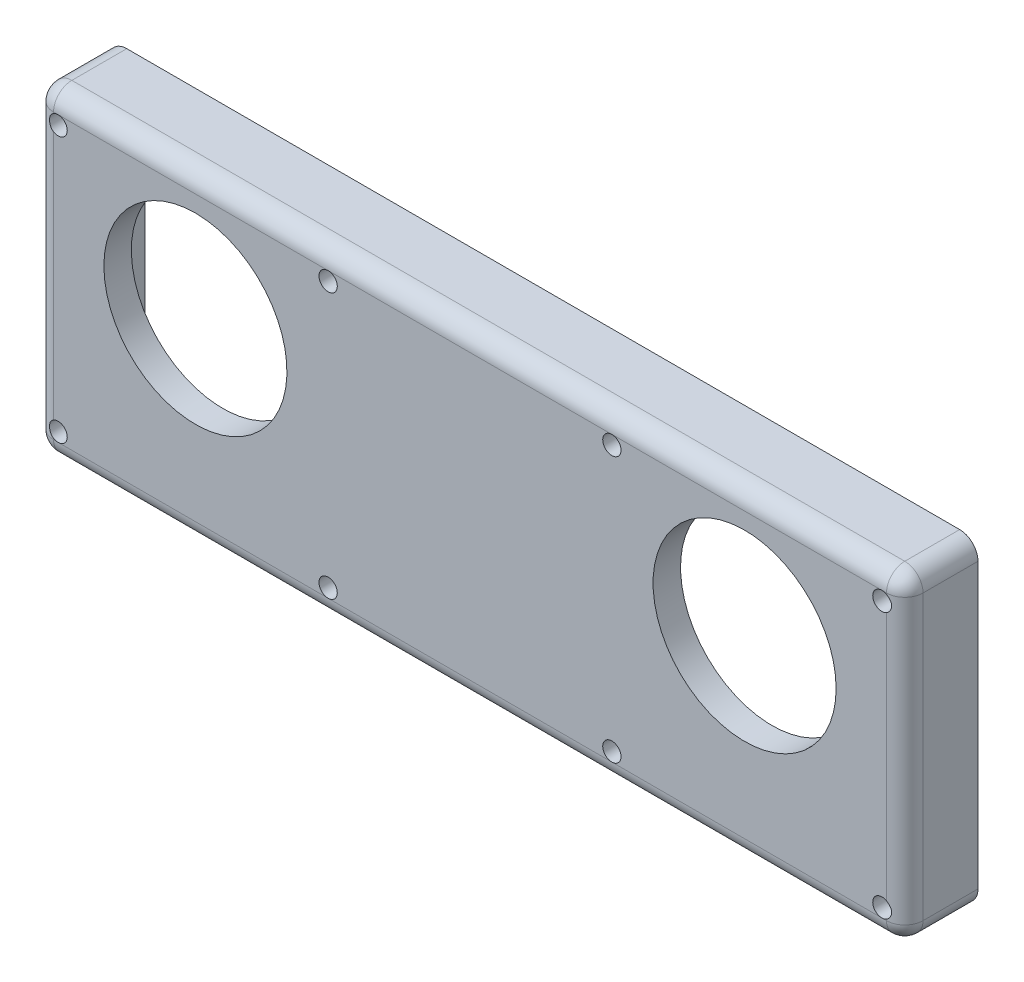
SolidWorks part; units mm, degrees
ref_plane "Front Plane" through (0, 0, 0) normal (0, 0, 1) x (1, 0, 0)
ref_plane "Top Plane" through (0, 0, 0) normal (0, 1, 0) x (1, 0, 0)
ref_plane "Right Plane" through (0, 0, 0) normal (1, 0, 0) x (0, 0, -1)
sketch "Sketch2" plane through (0, 0, 0) normal (0, 0, 1) x (1, 0, 0)
  line L0 (-59.1429, 44.8314) -> (33.8571, 44.8314)
  line L1 (33.8571, 44.8314) -> (33.8571, 12.8314)
  line L2 (33.8571, 12.8314) -> (-59.1429, 12.8314)
  line L3 (-59.1429, 12.8314) -> (-59.1429, 44.8314)
  circle A0 centre (-57.6429, 43.3314) radius 1
  circle A1 centre (-57.6429, 14.3314) radius 1
  circle A2 centre (-28.1429, 43.3314) radius 1
  circle A3 centre (2.8571, 43.3314) radius 1
  circle A4 centre (2.8571, 14.3314) radius 1
  circle A5 centre (-28.1429, 14.3314) radius 1
  circle A6 centre (32.3571, 14.3314) radius 1
  circle A7 centre (32.3571, 43.3314) radius 1
extrude "Boss-Extrude1" add sketch "Sketch2" along normal blind 3
sketch "Sketch6" plane through (0, 0, 3) normal (0, 0, 1) x (1, 0, 0)
  line L0 (-12.6429, 44.8314) -> (33.8571, 28.8314)
  line L1 (33.8571, 44.8314) -> (-59.1429, 44.8314) construction
  line L2 (33.8571, 12.8314) -> (33.8571, 44.8314) construction
  line L3 (33.8571, 28.8314) -> (-12.6429, 29.5401)
  line L5 (-60.1429, 12.0401) -> (34.8571, 12.0401)
  line L6 (-60.1429, 12.0401) -> (-60.1429, 47.0401)
  line L7 (-60.1429, 47.0401) -> (34.8571, 47.0401)
  line L8 (34.8571, 12.0401) -> (34.8571, 47.0401)
  line L9 (-60.1429, 12.0401) -> (34.8571, 47.0401) construction
  line L10 (-60.1429, 47.0401) -> (34.8571, 12.0401) construction
  line M1 (-59.1429, 44.8314) -> (-59.1429, 12.8314)
  line M2 (-59.1429, 12.8314) -> (33.8571, 12.8314)
  line M3 (33.8571, 12.8314) -> (33.8571, 44.8314)
  line M4 (33.8571, 44.8314) -> (-59.1429, 44.8314)
extrude "Boss-Extrude2" add sketch "Sketch6" against normal up to surface (3 mm away) contours L5 L8 L7 L6 M1 M4 M3 M2 region at (-60.0417, 29.5401, 3) up to face at (33.3571, 14.3314, 0)
sketch "Sketch8" plane through (0, 0, 0) normal (0, 0, -1) x (-1, 0, 0)
  line L0 (-34.8571, 47.0401) -> (-34.8571, 46.3314)
  line L1 (-34.8571, 12.0401) -> (-34.8571, 47.0401) construction
  line L2 (-32.8571, 46.3314) -> (58.1429, 46.3314) construction
  line L3 (-34.8571, 46.3314) -> (60.1429, 46.3314)
  line L4 (60.1429, 12.0401) -> (60.1429, 47.0401) construction
  line L5 (60.1429, 46.3314) -> (60.1429, 47.0401)
  line L6 (60.1429, 47.0401) -> (-34.8571, 47.0401)
extrude "Cut-Extrude6" cut sketch "Sketch8" against normal blind 10
sketch "Sketch9" plane through (0, 0, 3) normal (0, 0, 1) x (1, 0, 0)
  line L0 (34.8571, 12.0401) -> (34.8571, 11.3301)
  line L1 (-60.1429, 12.0401) -> (34.8571, 12.0401)
  line L2 (34.8571, 11.3301) -> (-60.1429, 11.3301)
  line L3 (-60.1429, 11.3301) -> (-60.1429, 12.0401)
extrude "Boss-Extrude3" add sketch "Sketch9" against normal up to surface (3 mm away) up to face at (-12.6429, 29.1858, 0)
sketch "Sketch10" plane through (0, 0, 3) normal (0, 0, 1) x (1, 0, 0)
  line L0 (-12.6429, 46.3314) -> (-68.5519, 3.7684)
  line L1 (34.8571, 46.3314) -> (-60.1429, 46.3314) construction
  line L2 (-68.5519, 3.7684) -> (-68.5519, 46.3314)
  line L3 (-68.5519, 46.3314) -> (17.3571, 46.3314)
  line L4 (17.3571, 46.3314) -> (17.3571, 32.5314)
  circle A0 centre (-68.5519, 3.7684) radius 10
  circle A1 centre (17.3571, 32.5314) radius 10
extrude "Cut-Extrude7" cut sketch "Sketch10" against normal blind 10 contours L2 A0 L0 | L0 A0 L2 | A1 region at (24.2282, 39.4025, 3) region at (-69.042, 2.7793, 3) region at (-65.6953, 9.5334, 3)
sketch "Sketch11" plane through (0, 0, 0) normal (0, 0, -1) x (-1, 0, 0)
  line L0 (60.1429, 11.3301) -> (-34.8571, 11.3301) construction
  line L1 (-34.8571, 46.3314) -> (60.1429, 46.3314)
  line L2 (-34.8571, 46.3314) -> (-34.8571, 11.3301)
  line L3 (-34.8571, 11.3301) -> (60.1429, 11.3301)
  line L4 (60.1429, 46.3314) -> (60.1429, 11.3301)
  line L5 (-34.8571, 46.3314) -> (60.1429, 11.3301)
  line L7 (-30.8571, 15.8308) -> (56.1429, 15.8308)
  line L8 (-30.8571, 15.8308) -> (-30.8571, 41.8308)
  line L9 (-30.8571, 41.8308) -> (56.1429, 41.8308)
  line L10 (56.1429, 15.8308) -> (56.1429, 41.8308)
  line L11 (-30.8571, 15.8308) -> (56.1429, 41.8308) construction
  line L12 (-30.8571, 41.8308) -> (56.1429, 15.8308) construction
  point P7 (12.6429, 28.8308)
  circle M2 centre (-17.3571, 32.5314) radius 10
  line M3 (60.1429, 46.3314) -> (-34.8571, 46.3314)
  line M4 (-34.8571, 46.3314) -> (-34.8571, 11.3301)
  line M5 (-34.8571, 11.3301) -> (60.1429, 11.3301)
  line M6 (60.1429, 11.3301) -> (60.1429, 46.3314)
  circle M7 centre (-32.3571, 14.3314) radius 1
  circle M8 centre (-2.8571, 14.3314) radius 1
  circle M9 centre (28.1429, 43.3314) radius 1
  circle M10 centre (57.6429, 43.3314) radius 1
  circle M11 centre (57.6429, 14.3314) radius 1
  circle M12 centre (-2.8571, 43.3314) radius 1
  circle M13 centre (28.1429, 14.3314) radius 1
  circle M14 centre (-32.3571, 43.3314) radius 1
extrude "Boss-Extrude7" add sketch "Sketch11" along normal blind 5 contours L10 L7 L5 L9 M6 M3 M2 M10 M12 M11 M9 | L8 L9 L5 L7 M4 M5 M7 M13 M14 M8 region at (29.0993, 43.1311, 0) region at (-12.6429, 45.319, 0)
fillet "Fillet1" radius 2 6 edges at (-12.6429, 11.3301, 3) (-12.6429, 46.3314, 3) (34.8571, 11.3301, -1) (34.8571, 46.3314, -1) (-60.1429, 46.3314, -1) (-60.1429, 11.3301, -1)
fillet "Fillet2" radius 2 6 edges at (34.2713, 11.9159, 2.4142) (34.2713, 45.7456, 2.4142) (-59.5571, 11.9159, 2.4142) (-59.5571, 45.7456, 2.4142) (34.8571, 28.8308, 3) (-60.1429, 28.8308, 3)
ref_plane "Plane1" through (-12.6429, 0, 0) normal (-1, 0, 0) x (0, 0, 1)
mirror "Mirror1" about plane through (-12.6429, 0, 0) normal (-1, 0, 0) of "Cut-Extrude7"
sketch "Sketch13" plane through (0, 0, -5) normal (0, 0, -1) x (-1, 0, 0)
  line L1 (-5.7553, 13.1072) -> (-4.6918, 13.1072)
  line L2 (12.6429, 15.8308) -> (12.6429, 11.3301)
  line L3 (-32.8571, 11.3301) -> (58.1429, 11.3301) construction
  line L4 (-0.8188, 13.1072) -> (0.2447, 13.1072)
  line L5 (0.2447, 13.1072) -> (0.2447, 14.1072)
  line L6 (0.2447, 14.1072) -> (-0.8188, 14.1072)
  line L7 (-4.6918, 14.1072) -> (-5.7553, 14.1072)
  line L8 (-5.7553, 14.1072) -> (-5.7553, 13.1072)
  line L9 (25.0412, 13.1072) -> (25.0412, 14.1072)
  line L10 (26.1047, 13.1072) -> (25.0412, 13.1072)
  line L11 (25.0412, 14.1072) -> (26.1047, 14.1072)
  line L12 (29.9776, 14.1072) -> (31.0412, 14.1072)
  line L13 (31.0412, 14.1072) -> (31.0412, 13.1072)
  line L14 (31.0412, 13.1072) -> (29.9776, 13.1072)
  arc A2 (-4.6918, 13.1072) -> (-0.8188, 13.1072) centre (-2.7553, 13.6072) ccw
  arc A3 (-0.8188, 14.1072) -> (-4.6918, 14.1072) centre (-2.7553, 13.6072) ccw
  arc A4 (26.1047, 14.1072) -> (29.9776, 14.1072) centre (28.0412, 13.6072) cw
  arc A5 (29.9776, 13.1072) -> (26.1047, 13.1072) centre (28.0412, 13.6072) cw
  circle M24 centre (-2.8571, 14.3314) radius 1
  circle M26 centre (28.1429, 14.3314) radius 1
extrude "Cut-Extrude9" cut sketch "Sketch13" against normal blind 2 contours M24 | M26 region at (5.6832, 13.6072, -5) region at (-25.1133, 13.6072, -5)
